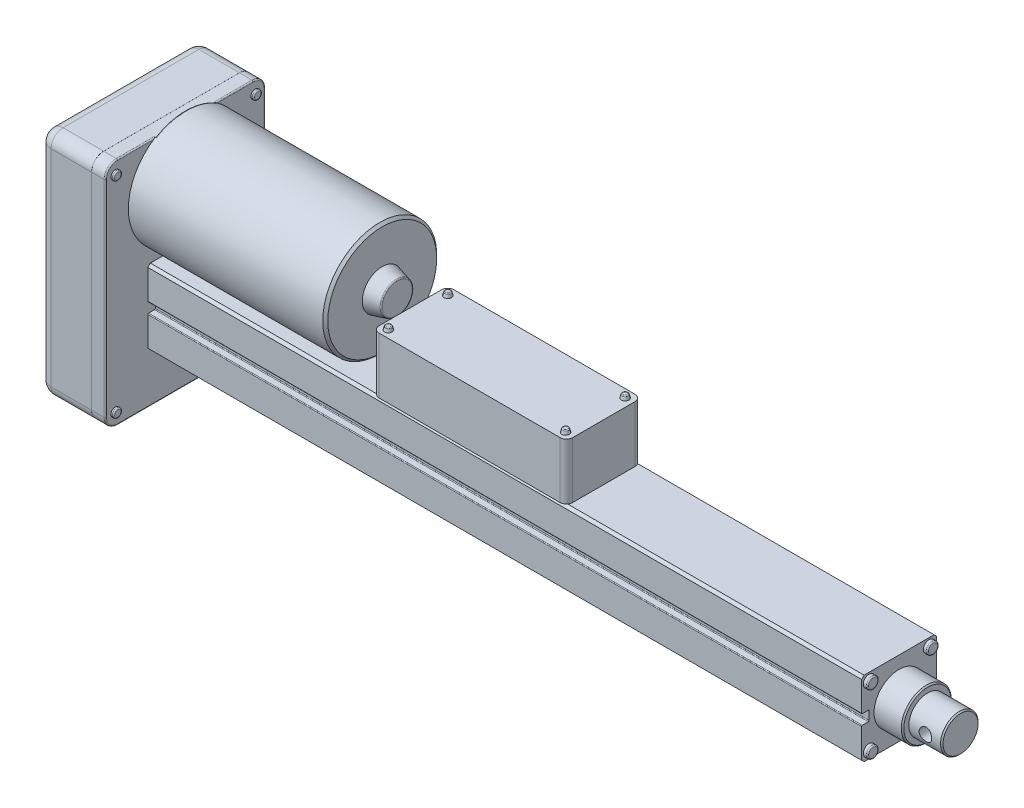
SolidWorks part; units mm, degrees
ref_plane "Front Plane" through (0, 0, 0) normal (0, 0, 1) x (1, 0, 0)
ref_plane "Top Plane" through (0, 0, 0) normal (0, 1, 0) x (1, 0, 0)
ref_plane "Right Plane" through (0, 0, 0) normal (1, 0, 0) x (0, 0, -1)
ref_plane "Plane1" through (-6.35, 0, 0) normal (-1, 0, 0) x (0, 0, 1)
sketch "Sketch1" plane through (-6.35, 0, 0) normal (-1, 0, 0) x (0, 0, 1)
  line L0 (-40.64, -43.942) -> (40.64, -43.942) construction
  line L5 (40.64, -43.942) -> (40.64, 73.152) construction
  line L6 (40.64, 73.152) -> (-40.64, 73.152) construction
  line L7 (-40.64, 73.152) -> (-40.64, -43.942) construction
  circle A0 centre (0, 0) radius 15.875 construction
  circle A1 centre (0, 0) radius 9.525 construction
  point P14 (0, -43.942)
  dimension "D3" = 19.05
  dimension "D4" = 31.75
  dimension "D2" = 73.152
  dimension "D1" = 43.942
  dimension "D5" = 81.28
sketch "Sketch2" plane through (0, 0, 0) normal (0, 0, 1) x (1, 0, 0)
  line L0 (0, 0) -> (46.228, 0) construction
  line L1 (10.668, 15.875) -> (10.668, -15.875)
  line L6 (10.668, 9.525) -> (-8.382, 9.525)
  line L7 (-8.382, 9.525) -> (-8.382, -9.525)
  line L8 (10.668, -15.875) -> (12.446, -15.875)
  line L9 (12.446, -15.875) -> (12.446, 15.875)
  line L10 (12.446, 15.875) -> (10.668, 15.875)
  line L11 (46.228, 0) -> (46.228, 48.514) construction
  line L12 (46.228, 48.514) -> (146.304, 48.514) construction
  line L13 (146.304, 77.47) -> (146.304, 19.558) construction
  line L14 (0, 0) -> (304.8, 0) construction
  line L15 (-8.382, 0) -> (440.182, 0) construction
  line L16 (46.228, 19.05) -> (408.94, 19.05)
  line L17 (46.228, 19.05) -> (46.228, -19.05)
  line L18 (46.228, -19.05) -> (408.94, -19.05)
  line L19 (408.94, 19.05) -> (408.94, -19.05)
  line L20 (408.94, 12.7) -> (423.418, 12.7)
  line L21 (408.94, 12.7) -> (408.94, -12.7)
  line L22 (408.94, -12.7) -> (423.418, -12.7)
  line L23 (423.418, 12.7) -> (423.418, -12.7)
  line L24 (423.418, 9.525) -> (440.182, 9.525)
  line L25 (423.418, 9.525) -> (423.418, -9.525)
  line L26 (423.418, -9.525) -> (440.182, -9.525)
  line L27 (440.182, 9.525) -> (440.182, -9.525)
  line L28 (-8.382, 0) -> (440.182, 0) construction
  line L29 (-8.382, -9.525) -> (10.668, -9.525)
  line L30 (10.668, -9.525) -> (10.668, 9.525)
  line L31 (-8.382, 0) -> (744.093, 0) construction
  circle A0 centre (0, 0) radius 3.175 construction
  circle A1 centre (431.8, 0) radius 3.175
  point P10 (10.668, 0)
  point P13 (46.228, 0)
  point P18 (46.228, 48.514)
  point P21 (146.304, 48.514)
  point P23 (146.304, 77.47)
  point P24 (146.304, 19.558)
  point P28 (46.228, 0)
  point P31 (408.94, 0)
  point P33 (408.94, 0)
  point P38 (423.418, 0)
  point P39 (423.418, 0)
  point P42 (431.8, 9.525)
  point P48 (10.668, 0)
  dimension "D2" = 6.35
  dimension "D6" = 31.75
  dimension "D7" = 46.228
  dimension "D8" = 48.514
  dimension "D10" = 57.912
  dimension "D11" = 408.94
  dimension "Stroke Lg" = 304.8
  dimension "D12" = 38.1
  dimension "D14" = 431.8
  dimension "D15" = 19.05
  dimension "D3" = 10.668
  dimension "D4" = 8.382
  dimension "D5" = 19.05
  dimension "D16" = 1.778
  dimension "D17" = 448.564
  dimension "D13" = 8.382
  dimension "D18" = 25.4
  dimension "Extended Lg2" = 752.475
  dimension "D9" = 146.304
sketch "Sketch3" plane through (0, 0, 0) normal (0, 0, 1) x (1, 0, 0)
  line L0 (12.446, 15.875) -> (10.668, 15.875)
  line L1 (-8.382, 9.525) -> (-8.382, 0)
  line L2 (440.182, 9.525) -> (440.182, -9.525) construction
  line L7 (10.668, 15.875) -> (10.668, 9.525)
  line L13 (408.94, 12.7) -> (423.418, 12.7)
  line L14 (423.418, 12.7) -> (423.418, 9.525)
  line L15 (423.418, 9.525) -> (440.182, 9.525)
  line L16 (440.182, 9.525) -> (440.182, 0)
  line L19 (440.182, 0) -> (408.94, 0)
  line L20 (408.94, 0) -> (408.94, 12.7)
  line L21 (10.668, 9.525) -> (-8.382, 9.525)
  line L24 (-8.382, 0) -> (12.446, 0)
  line L25 (12.446, -15.875) -> (12.446, 15.875) construction
  line L26 (12.446, 0) -> (12.446, 15.875)
  line L27 (-8.382, 0) -> (440.182, 0) construction
revolve "Revolve1" add sketch "Sketch3" angle 360 about L24
sketch "Sketch4" plane through (0, 0, 0) normal (0, 0, 1) x (1, 0, 0)
  line L0 (46.228, 19.05) -> (46.228, -19.05) construction
  line L1 (46.228, -19.05) -> (408.94, -19.05) construction
  line L2 (408.94, 19.05) -> (408.94, -19.05) construction
  line L3 (46.228, 19.05) -> (408.94, 19.05) construction
  line L4 (46.228, 19.05) -> (46.228, -19.05)
  line L5 (46.228, -19.05) -> (408.94, -19.05)
  line L6 (408.94, 19.05) -> (408.94, -19.05)
  line L7 (46.228, 19.05) -> (408.94, 19.05)
extrude "Boss-Extrude1" add sketch "Sketch4" along normal mid plane 38.1
sketch "Sketch5" plane through (0, 0, 0) normal (0, 0, 1) x (1, 0, 0)
  line L5 (146.304, 48.514) -> (46.228, 48.514)
  line L6 (146.304, 48.514) -> (146.304, 77.47)
  line L7 (146.304, 77.47) -> (46.228, 77.47)
  line L8 (46.228, 48.514) -> (46.228, 77.47)
revolve "Revolve2" add sketch "Sketch5" angle 360 about L12
sketch "Sketch9" plane through (12.446, 0, 0) normal (1, 0, 0) x (0, 0, -1)
  line L0 (40.64, -43.942) -> (-40.64, -43.942) construction
  line L1 (-40.64, -43.942) -> (-40.64, 73.152) construction
  line L2 (40.64, 73.152) -> (40.64, -43.942) construction
  line L3 (-40.64, 73.152) -> (40.64, 73.152) construction
  line L4 (40.64, -43.942) -> (-40.64, -43.942)
  line L5 (-40.64, -43.942) -> (-40.64, 73.152)
  line L6 (40.64, 73.152) -> (40.64, -43.942)
  line L7 (-40.64, 73.152) -> (40.64, 73.152)
extrude "Boss-Extrude3" add sketch "Sketch9" along normal up to vertex (33.782 mm away) up to point (46.228, -19.05, 0)
sketch "Sketch10" plane through (0, 0, 0) normal (0, 0, 1) x (1, 0, 0)
  line L0 (46.228, -19.05) -> (408.94, -19.05) construction
  line L1 (50.7276, -19.05) -> (149.1324, -19.05)
  line L2 (50.7276, -19.05) -> (50.7276, -47.625)
  line L3 (50.7276, -47.625) -> (149.1324, -47.625)
  line L4 (149.1324, -19.05) -> (149.1324, -47.625)
  dimension "D1" = 4.4996
  dimension "D2" = 28.575
  dimension "D3" = 98.4048
extrude "Boss-Extrude4" add sketch "Sketch10" along normal mid plane 38.1 separate body
chamfer "Chamfer1" distance 1.27 angle 45 4 edges at (227.584, 19.05, 19.05) (227.584, -19.05, 19.05) (227.584, -19.05, -19.05) (227.584, 19.05, -19.05)
fillet "Fillet1" radius 6.1549 8 edges at (12.446, -43.942, 0) (12.446, 14.605, 40.64) (12.446, 14.605, -40.64) (12.446, 73.152, 0) (29.337, -43.942, 40.64) (29.337, 73.152, 40.64) (29.337, 73.152, -40.64) (29.337, -43.942, -40.64)
chamfer "Chamfer2" distance 0.635 angle 45 3 edges at (423.418, 0, 12.7) (440.182, 0, 9.525) (-8.382, 0, 9.525)
sketch "Sketch13" plane through (408.94, 0, 0) normal (1, 0, 0) x (0, 0, -1)
  line L1 (-15.24, -15.24) -> (15.24, -15.24) construction
  line L2 (-15.24, -15.24) -> (-15.24, 15.24) construction
  line L3 (-15.24, 15.24) -> (15.24, 15.24) construction
  line L4 (15.24, -15.24) -> (15.24, 15.24) construction
  line L5 (-15.24, -15.24) -> (15.24, 15.24) construction
  line L6 (-15.24, 15.24) -> (15.24, -15.24) construction
  circle A0 centre (15.24, 15.24) radius 2.921
  circle A1 centre (-15.24, 15.24) radius 2.921
  circle A2 centre (15.24, -15.24) radius 2.921
  circle A3 centre (-15.24, -15.24) radius 2.921
  point P0 (0, 0)
  dimension "D2" = 5.842
  dimension "D1" = 30.48
extrude "Boss-Extrude5" add sketch "Sketch13" along normal blind 2.0828
fillet "Fillet2" radius 3.175 4 edges at (50.7276, -33.3375, 19.05) (50.7276, -33.3375, -19.05) (149.1324, -33.3375, -19.05) (149.1324, -33.3375, 19.05)
fillet "Fillet5" radius 0.635 1 edges at (46.228, 77.47, 0)
fillet "Fillet8" radius 0.635 9 edges at (46.228, 73.152, 24.8488) (46.228, 71.3493, 38.8373) (46.228, 73.152, -24.8488) (46.228, 71.3493, -38.8373) (46.228, 14.605, -40.64) (46.228, -42.1393, -38.8373) (46.228, -43.942, 0) (46.228, -42.1393, 38.8373) (46.228, 14.605, 40.64)
sketch "Sketch16" plane through (0, 0, 0) normal (0, 0, 1) x (1, 0, 0)
  circle A0 centre (0, 0) radius 3.175 construction
  circle A1 centre (431.8, 0) radius 3.175 construction
  circle A2 centre (0, 0) radius 3.175
  circle A3 centre (431.8, 0) radius 3.175
extrude "Cut-Extrude1" cut sketch "Sketch16" against normal through all both and the other way through all
sketch "Sketch21" plane through (0, -47.625, 0) normal (0, -1, 0) x (1, 0, 0)
  line L20 (54.8941, 14.939) -> (144.966, 14.939) construction
  line L21 (144.966, 14.939) -> (144.966, -15.2616) construction
  line L22 (144.966, -15.2616) -> (54.8941, -15.2616) construction
  line L23 (54.8941, -15.2616) -> (54.8941, 14.939) construction
  line L24 (53.9026, 19.05) -> (145.9574, 19.05) construction
  circle A0 centre (144.966, 14.939) radius 1.905
  circle A1 centre (144.966, -15.2616) radius 1.905
  circle A2 centre (54.8941, -15.2616) radius 1.905
  circle A3 centre (54.8941, 14.939) radius 1.905
  point P10 (99.93, 19.05)
  point P11 (99.93, 14.939)
  dimension "D1" = 3.81
  dimension "D2" = 90.0719
  dimension "D3" = 30.2006
  dimension "D4" = 4.111
extrude "Boss-Extrude12" add sketch "Sketch21" along normal blind 1.905 draft 15
sketch "Sketch23" plane through (46.228, 0, 0) normal (1, 0, 0) x (0, 0, -1)
  line L0 (-35.56, 66.802) -> (35.56, 66.802) construction
  line L1 (35.56, 66.802) -> (35.56, -37.592) construction
  line L2 (35.56, -37.592) -> (-35.56, -37.592) construction
  line L3 (-35.56, -37.592) -> (-35.56, 66.802) construction
  line L4 (-35.56, 14.605) -> (35.56, 14.605) construction
  line L5 (15.2125, 73.152) -> (34.4851, 73.152) construction
  line L7 (40.64, 66.9971) -> (40.64, -37.7871) construction
  circle A0 centre (-35.56, -37.592) radius 2.2225
  circle A1 centre (35.56, -37.592) radius 2.2225
  circle A2 centre (35.56, 66.802) radius 2.2225
  circle A3 centre (-35.56, 66.802) radius 2.2225
  point P10 (0, 14.605)
  dimension "D1" = 6.35
  dimension "D3" = 4.445
  dimension "D2" = 6.35
  dimension "D4" = 5.08
extrude "Boss-Extrude13" add sketch "Sketch23" along normal blind 1.27
move or copy body "Body-Move/Copy4" bodies to move or copy 126 copy no translate (109.8004, 63.5, 0)
move or copy body "Body-Move/Copy5" bodies to move or copy 122 copy no rotation origin (0, 31.75, 0) rotation axis (1, 0, 0) rotation angle 180
sketch "Sketch18" plane through (0, -19.05, 0) normal (0, -1, 0) x (1, 0, 0)
  line L0 (46.228, 0) -> (52.578, 0) construction
  line L1 (46.228, 0) -> (408.94, 0) construction
  line L2 (408.94, -12.7) -> (408.94, 12.7) construction
  line L3 (52.578, 4.318) -> (82.296, 4.318)
  line L4 (52.578, 4.318) -> (52.578, -4.318)
  line L5 (52.578, -4.318) -> (82.296, -4.318)
  line L6 (82.296, 4.318) -> (82.296, -4.318)
  line L7 (353.822, 4.318) -> (383.54, 4.318)
  line L8 (353.822, 4.318) -> (353.822, -4.318)
  line L9 (353.822, -4.318) -> (383.54, -4.318)
  line L10 (383.54, 4.318) -> (383.54, -4.318)
  point P10 (52.578, 0)
  point P15 (353.822, 0)
  dimension "D1" = 6.35
  dimension "D2" = 8.636
  dimension "D3" = 29.718
  dimension "D4" = 25.4
extrude "Boss-Extrude9" add sketch "Sketch18" along normal blind 5.08
sketch "Sketch19" plane through (0, 0, 0) normal (0, 0, 1) x (1, 0, 0)
  line L0 (411.0228, 12.319) -> (744.093, 12.319) construction
  line L1 (744.093, 12.319) -> (744.093, -12.7) construction
  line L3 (408.94, -12.7) -> (744.093, -12.7) construction
  line L4 (-8.382, 0) -> (744.093, 0) construction
  line L8 (744.093, 9.525) -> (727.329, 9.525) construction
  line L9 (727.329, 9.525) -> (727.329, 12.319) construction
  line L16 (744.093, -9.525) -> (727.329, -9.525) construction
  line L17 (727.329, -9.525) -> (727.329, -12.7) construction
  line L18 (423.418, -9.525) -> (440.182, -9.525) construction
  line L19 (423.418, 9.525) -> (440.182, 9.525) construction
  line L20 (408.94, -12.7) -> (727.329, -12.7)
  line L21 (727.329, -12.7) -> (727.329, -9.525)
  line L22 (727.329, -9.525) -> (744.093, -9.525)
  line L23 (744.093, -9.525) -> (744.093, 9.525)
  line L24 (744.093, 9.525) -> (727.329, 9.525)
  line L25 (727.329, 9.525) -> (727.329, 12.319)
  line L26 (727.329, 12.319) -> (411.0228, 12.319)
  circle A1 centre (735.711, 0) radius 3.175
  circle A2 centre (431.8, 0) radius 3.175 construction
  dimension "D1" = 8.382
fillet "Fillet13" radius 0.508 4 edges at (254.7663, 49.53, -13.5444) (254.7663, 49.53, 16.6561) (164.6945, 49.53, -13.5444) (164.6945, 49.53, 16.6561)
sketch "Sketch27" plane through (0, -24.13, 0) normal (0, -1, 0) x (1, 0, 0)
  line L0 (52.578, 0) -> (54.737, 0) construction
  line L1 (52.578, 4.318) -> (52.578, -4.318) construction
  line L2 (54.737, 0) -> (80.137, 0) construction
  line L3 (80.137, 0) -> (82.296, 0) construction
  line L4 (82.296, -4.318) -> (82.296, 4.318) construction
  line L5 (353.822, 0) -> (355.981, 0) construction
  line L6 (353.822, 4.318) -> (353.822, -4.318) construction
  line L7 (355.981, 0) -> (381.381, 0) construction
  line L8 (381.381, 0) -> (383.54, 0) construction
  line L9 (383.54, -4.318) -> (383.54, 4.318) construction
  circle A0 centre (54.737, 0) radius 1.27
  circle A1 centre (80.137, 0) radius 1.27
  circle A2 centre (355.981, 0) radius 1.27
  circle A3 centre (381.381, 0) radius 1.27
  dimension "D2" = 2.54
  dimension "D4" = 2.54
  dimension "D1" = 25.4
  dimension "D3" = 25.4
extrude "Boss-Extrude17" add sketch "Sketch27" along normal blind 0.508
fillet "Fillet16" radius 0.381 20 edges at (80.137, -24.638, -1.27) (383.54, -21.59, 4.318) (353.822, -24.13, 0) (353.822, -21.59, 4.318) (353.822, -21.59, -4.318) (368.681, -24.13, 4.318) (383.54, -24.13, 0) (383.54, -21.59, -4.318) (368.681, -24.13, -4.318) (381.381, -24.638, -1.27) (355.981, -24.638, -1.27) (54.737, -24.638, -1.27) (67.437, -24.13, -4.318) (52.578, -21.59, -4.318) (82.296, -24.13, 0) (82.296, -21.59, -4.318) (82.296, -21.59, 4.318) (67.437, -24.13, 4.318) (52.578, -24.13, 0) (52.578, -21.59, 4.318)
chamfer "Chamfer3" distance 1.27 angle 45 1 edges at (146.304, 48.514, 28.956)
sketch "Sketch29" plane through (146.304, 0, 0) normal (1, 0, 0) x (0, 0, -1)
  circle A0 centre (0, 48.514) radius 10.16
  dimension "D1" = 20.32
extrude "Boss-Extrude18" add sketch "Sketch29" along normal blind 7.62 draft 15
fillet "Fillet17" radius 0.635 9 edges at (153.924, 48.514, -8.1182) (47.498, -37.592, 33.3375) (47.498, 66.802, 33.3375) (47.498, -37.592, -37.7825) (411.0228, -15.24, -18.161) (411.0228, -15.24, 12.319) (411.0228, 15.24, 12.319) (411.0228, 15.24, -18.161) (47.498, 66.802, -37.7825)
sketch "Sketch30" plane through (0, 0, 40.64) normal (0, 0, 1) x (1, 0, 0)
  line L0 (39.243, 73.152) -> (39.243, -43.942)
  line L1 (18.6009, 73.152) -> (45.593, 73.152) construction
  line L2 (45.593, -43.942) -> (18.6009, -43.942) construction
  line L3 (45.593, -37.7871) -> (45.593, 66.9971) construction
  dimension "D1" = 6.35
extrude "Cut-Extrude-Thin1" cut sketch "Sketch30" against normal through all and the other way through all thin thin type one direction wall 0.0254
sketch "Sketch31" plane through (0, 0, 19.05) normal (0, 0, 1) x (1, 0, 0)
  line L1 (46.228, 2.54) -> (408.94, 2.54)
  line L3 (46.228, -2.54) -> (408.94, -2.54)
  line L4 (408.94, 2.54) -> (408.94, -2.54)
  line L5 (408.94, -17.78) -> (408.94, 17.78) construction
  line L8 (46.228, 2.54) -> (46.228, -2.54)
  line L9 (46.228, 17.78) -> (46.228, -17.78) construction
  point P8 (46.228, 0)
  dimension "D1" = 5.08
extrude "Cut-Extrude2" cut sketch "Sketch31" against normal blind 3.81
fillet "Fillet18" radius 0.381 4 edges at (227.584, -2.54, 19.05) (227.584, 2.54, 19.05) (227.584, 2.54, 15.24) (227.584, -2.54, 15.24)
ref_plane "Contact Plane 1" through (0, 73.152, 0) normal (0, 1, 0) x (1, 0, 0)
ref_plane "Contact Plane 2" through (0, -43.942, 0) normal (0, -1, 0) x (-1, 0, 0)
ref_plane "Contact Plane 3" through (12.446, 0, 0) normal (-1, 0, 0) x (0, 0, 1)
ref_plane "Contact Plane 4" through (-8.382, 0, 0) normal (-1, 0, 0) x (0, 0, 1)
ref_plane "Contact Plane 5" through (440.182, 0, 0) normal (1, 0, 0) x (0, 0, -1)
ref_axis "Center Axis 1" through (0, 0, -9.525) along (0, 0, 1)
ref_axis "Center Axis 2" through (431.8, 0, -9.525) along (0, 0, 1)
equation "\"D6@Sketch2\"=\"D4@Sketch1\""
equation "\"D11@Sketch2\"=\"Stroke Lg@Sketch2\"+4.1"
equation "\"D14@Sketch2\"=\"Stroke Lg@Sketch2\"+5"
equation "\"D1@Boss-Extrude1\"=\"D12@Sketch2\""
equation "\"D5@Sketch2\"=\"D3@Sketch1\""
equation "\"D1@Sketch19\"=\"D13@Sketch2\""
